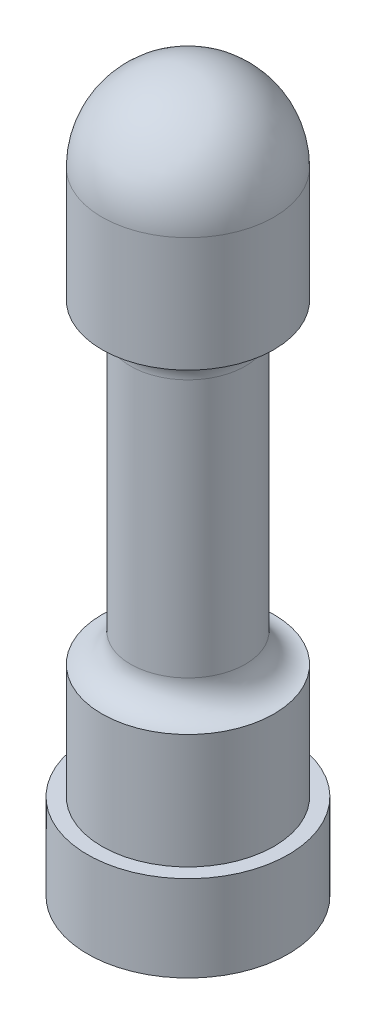
SolidWorks part; units mm, degrees
ref_plane "Front Plane" through (0, 0, 0) normal (0, 0, 1) x (1, 0, 0)
ref_plane "Top Plane" through (0, 0, 0) normal (0, 1, 0) x (1, 0, 0)
ref_plane "Right Plane" through (0, 0, 0) normal (1, 0, 0) x (0, 0, -1)
sketch "Sketch1" plane through (0, 0, 0) normal (0, 0, 1) x (1, 0, 0)
  line L0 (3, 18) -> (2, 18)
  line L1 (0, 0) -> (3.5, 0)
  line L2 (0, 0) -> (0, 25)
  line L3 (0, 25) -> (3, 25)
  line L4 (3.5, 0) -> (3.5, 3)
  line L5 (2, 18) -> (2, 7)
  line L6 (2, 7) -> (3, 7)
  line L7 (3, 7) -> (3, 3)
  line L8 (3, 3) -> (3.5, 3)
  line L9 (3, 18) -> (3, 25)
  point P1 (0, 0)
  point P12 (2, 13.0149)
  dimension "D1" = 3.5
  dimension "D2" = 3
  dimension "D3" = 2
  dimension "D4" = 3
  dimension "D5" = 3
  dimension "D6" = 4
  dimension "D7" = 11
  dimension "D8" = 7
revolve "Revolve1" add sketch "Sketch1" angle 360 about L2
fillet "Fillet1" radius 3 1 edges at (0, 25, -3)
fillet "Fillet2" radius 1 2 edges at (0, 7, -2) (0, 18, -2)
sketch "Sketch2" plane through (0, 0, 0) normal (0, 0, 1) x (1, 0, 0)
  line L0 (0, 0) -> (0, 1.5)
  line L1 (0, 0) -> (1.5, 0)
  line L2 (-3.5, 0) -> (3.5, 0) construction
  arc A0 (0, 1.5) -> (1.5, 0) centre (0, 0) cw
  point P7 (0, 0)
  dimension "D1" = 1.5
revolve "Cut-Revolve1" cut sketch "Sketch2" angle 360 about L0
